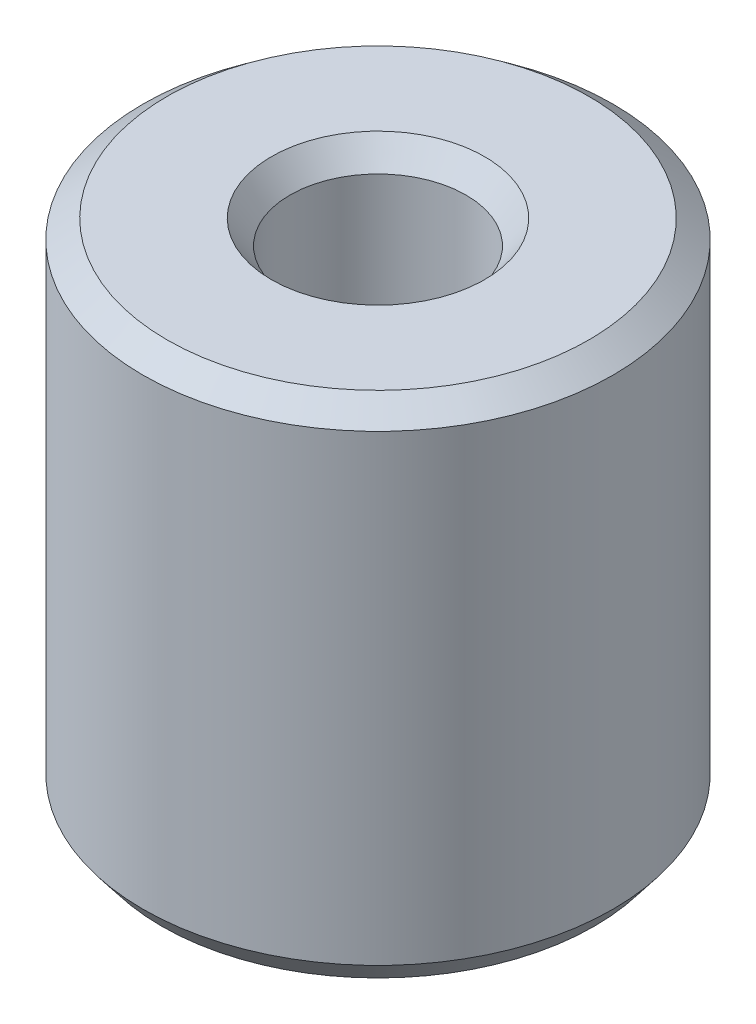
SolidWorks part; units mm, degrees
ref_plane "Front Plane" through (0, 0, 0) normal (0, 0, 1) x (1, 0, 0)
ref_plane "Top Plane" through (0, 0, 0) normal (0, 1, 0) x (1, 0, 0)
ref_plane "Right Plane" through (0, 0, 0) normal (1, 0, 0) x (0, 0, -1)
sketch "Sketch1" plane through (0, 0, 0) normal (0, 1, 0) x (1, 0, 0)
  circle A0 centre (0, 0) radius 7.5
  dimension "SLEEVE_OD" = 15
extrude "Boss-Extrude1" add sketch "Sketch1" along normal blind 16.1252
sketch "Sketch2" plane through (0, 0, 0) normal (0, 1, 0) x (1, 0, 0)
  circle A0 centre (0, 0) radius 2.811
  dimension "BORE_D" = 5.6221
extrude "Cut-Extrude1" cut sketch "Sketch2" along normal through all
chamfer "Chamfer1" distance 0.5927 angle 52.27 4 edges at (0, 16.1252, 2.811) (0, 0, 2.811) (0, 0, 7.5) (0, 16.1252, 7.5) first distance on face at (0, 16.1252, 2.811) first distance on face at (0, 0, 2.811) first distance on face at (0, 16.1252, 7.5)
